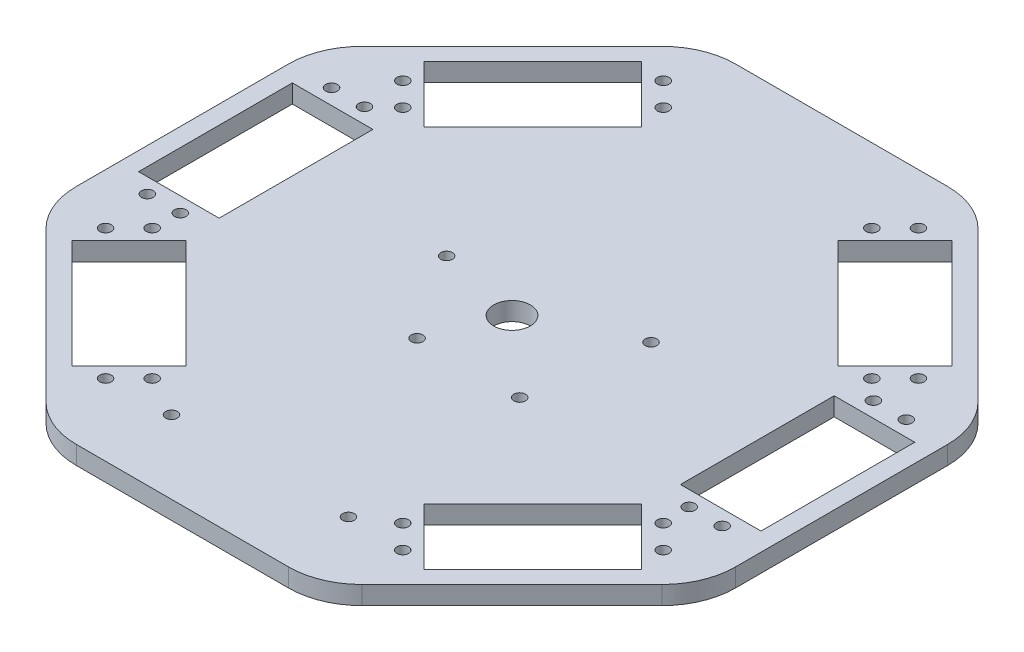
SolidWorks part; units mm, degrees
ref_plane "Front Plane" through (0, 0, 0) normal (0, 0, 1) x (1, 0, 0)
ref_plane "Top Plane" through (0, 0, 0) normal (0, 1, 0) x (1, 0, 0)
ref_plane "Right Plane" through (0, 0, 0) normal (1, 0, 0) x (0, 0, -1)
sketch "Sketch1" plane through (0, 0, 0) normal (0, 1, 0) x (1, 0, 0)
  line L1 (-90, -37.2792) -> (-37.2792, -90)
  line L2 (-37.2792, -90) -> (37.2792, -90)
  line L3 (37.2792, -90) -> (90, -37.2792)
  line L4 (90, -37.2792) -> (90, 37.2792)
  line L5 (90, 37.2792) -> (37.2792, 90)
  line L6 (37.2792, 90) -> (-37.2792, 90)
  line L7 (-37.2792, 90) -> (-90, 37.2792)
  line L8 (-90, 37.2792) -> (-90, -37.2792)
  line L12 (63.6396, -63.6396) -> (0, 0) construction
  line L21 (-20.4, -34.5422) -> (-34.5422, -20.4)
  line L22 (-20.4, -34.5422) -> (-50.0985, -64.2407)
  line L23 (-50.0985, -64.2407) -> (-64.2407, -50.0985)
  line L24 (-34.5422, -20.4) -> (-64.2407, -50.0985)
  line L25 (-38.85, -10) -> (-38.85, 10)
  line L26 (-38.85, -10) -> (-80.85, -10)
  line L27 (-80.85, -10) -> (-80.85, 10)
  line L28 (-38.85, 10) -> (-80.85, 10)
  line L29 (-34.5422, 20.4) -> (-20.4, 34.5422)
  line L30 (-34.5422, 20.4) -> (-64.2407, 50.0985)
  line L31 (-64.2407, 50.0985) -> (-50.0985, 64.2407)
  line L32 (-20.4, 34.5422) -> (-50.0985, 64.2407)
  line L37 (20.4, 34.5422) -> (34.5422, 20.4)
  line L38 (20.4, 34.5422) -> (50.0985, 64.2407)
  line L39 (50.0985, 64.2407) -> (64.2407, 50.0985)
  line L40 (34.5422, 20.4) -> (64.2407, 50.0985)
  line L41 (38.85, 10) -> (38.85, -10)
  line L42 (38.85, 10) -> (80.85, 10)
  line L43 (80.85, 10) -> (80.85, -10)
  line L44 (38.85, -10) -> (80.85, -10)
  circle A0 centre (0, 0) radius 90 construction
  circle A13 centre (0, 0) radius 90 construction
  circle A14 centre (-27.7186, -21.3546) radius 2.5
  circle A15 centre (-21.3546, -27.7186) radius 2.5
  circle A16 centre (-56.9221, -63.2861) radius 2.5
  circle A17 centre (-63.2861, -56.9221) radius 2.5
  circle A18 centre (0, 0) radius 90 construction
  circle A19 centre (-34.7, 4.5) radius 2.5
  circle A20 centre (-34.7, -4.5) radius 2.5
  circle A21 centre (-85, -4.5) radius 2.5
  circle A22 centre (-85, 4.5) radius 2.5
  circle A23 centre (0, 0) radius 90 construction
  circle A24 centre (-21.3546, 27.7186) radius 2.5
  circle A25 centre (-27.7186, 21.3546) radius 2.5
  circle A26 centre (-63.2861, 56.9221) radius 2.5
  circle A27 centre (-56.9221, 63.2861) radius 2.5
  circle A28 centre (0, 0) radius 90 construction
  circle A33 centre (0, 0) radius 90 construction
  circle A34 centre (27.7186, 21.3546) radius 2.5
  circle A35 centre (21.3546, 27.7186) radius 2.5
  circle A36 centre (56.9221, 63.2861) radius 2.5
  circle A37 centre (63.2861, 56.9221) radius 2.5
  circle A38 centre (0, 0) radius 90 construction
  circle A39 centre (34.7, -4.5) radius 2.5
  circle A40 centre (34.7, 4.5) radius 2.5
  circle A41 centre (85, 4.5) radius 2.5
  circle A42 centre (85, -4.5) radius 2.5
  circle A43 centre (0, 0) radius 90 construction
  point P15 (63.6396, -63.6396)
  point P16 (60.1041, -60.1041)
  point P17 (57.1696, -57.1696)
  point P121 (0, 0)
  dimension "D1" = 90
  dimension "D12" = 8
extrude "Baseplate" add sketch "Sketch1" along normal blind 5 contours L7 L8 L1 L2 L3 L4 L5 L6 A42 A41 A40 A39 A37 A36 A35 A34 A27 A26 A25 A24 A22 A21 A20 A19 A17 A16 A15 A14 L44 L41 | L29 L32 L31 L30 | L37 L40 L39 L38 | L41 L44 L43 L42 | L25 L28 L27 L26 | A27 | A26 | A25 | A24 | A22 | A21 | A19 | A20 | A14 | A15 | A17 | A16 | A40 | A41 | A42 | A35 | A34 | A39 | A37 | A36 | L21 L24 L23 L22 region at (1.7472, 0, 1.7472) region at (-59.85, 0, 0) region at (-42.3203, 0, -42.3203) region at (42.3203, 0, -42.3203) region at (59.85, 0, 0) region at (-27.7186, 0, 21.3546) region at (-21.3546, 0, 27.7186) region at (-56.9221, 0, 63.2861) region at (-63.2861, 0, 56.9221) region at (-34.7, 0, -4.5) region at (-34.7, 0, 4.5) region at (-85, 0, 4.5) region at (-85, 0, -4.5) region at (-21.3546, 0, -27.7186) region at (-27.7186, 0, -21.3546) region at (-63.2861, 0, -56.9221) region at (-56.9221, 0, -63.2861) region at (34.7, 0, -4.5) region at (85, 0, -4.5) region at (85, 0, 4.5)
fillet "Fillet1" radius 20 8 edges at (-90, 2.5, -37.2792) (-37.2792, 2.5, -90) (37.2792, 2.5, -90) (90, 2.5, -37.2792) (90, 2.5, 37.2792) (37.2792, 2.5, 90) (-37.2792, 2.5, 90) (-90, 2.5, 37.2792)
sketch "Sketch2" plane through (0, 5, 0) normal (0, 1, 0) x (1, 0, 0)
  line L0 (90, -28.9949) -> (90, 28.9949) construction
  line L1 (63, 25.0051) -> (85, 25.0051)
  line L2 (63, 25.0051) -> (63, -16.9949)
  line L3 (63, -16.9949) -> (85, -16.9949)
  line L4 (85, 25.0051) -> (85, -16.9949)
  circle A0 centre (78.5, 29.2051) radius 1.6
  circle A1 centre (69.5, 29.2051) radius 1.6
  circle A2 centre (69.5, -21.0949) radius 1.6
  circle A3 centre (78.5, -21.0949) radius 1.6
  point P8 (74, 25.0051)
  dimension "D1" = 3.2
  dimension "D2" = 9
  dimension "D3" = 50.3
  dimension "D4" = 22
  dimension "D5" = 42
  dimension "D6" = 4.2
  dimension "D7" = 4.5
  dimension "D8" = 5
  dimension "D9" = 12
extrude "Servo hole" cut sketch "Sketch2" against normal through all contours A0 | L4 L1 L2 L3 | A2 | A3 | A1 region at (74, 5, -4.0051) region at (78.5, 5, -29.2051) region at (69.5, 5, 21.0949) region at (78.5, 5, 21.0949)
sketch "Sketch3" plane through (0, 5, 0) normal (0, 1, 0) x (1, 0, 0)
  circle A0 centre (0, 0) radius 5
  dimension "D1" = 10
extrude "Center hole" cut sketch "Sketch3" against normal through all
pattern_circular "Servo hole pattern" count 8 over 360 about axis through (0, 5, 0) along (0, 1, 0) skipping 2, 3, 4, 5, 6 of "Servo hole"
sketch "Sketch4" plane through (0, 5, 0) normal (0, 1, 0) x (1, 0, 0)
  line L0 (-28.9949, -90) -> (28.9949, -90) construction
  line L1 (-90, 28.9949) -> (-90, -28.9949) construction
  circle A0 centre (-23, 5.1332) radius 1.6
  circle A1 centre (-23, -70) radius 1.6
  circle A2 centre (25.3362, 12.6262) radius 1.6
  circle A3 centre (25.3362, -70) radius 1.6
  circle A4 centre (-7.5585, -18.3745) radius 1.6
  circle A5 centre (20.4577, -18.3745) radius 1.6
  dimension "D1" = 3.2
  dimension "D8" = 20
  dimension "D2" = 7.493
  dimension "D3" = 48.3362
  dimension "D4" = 31.0007
  dimension "D5" = 51.6255
  dimension "D6" = 4.8785
  dimension "D7" = 28.0162
  dimension "D9" = 67
extrude "Arduino Screw holes" cut sketch "Sketch4" against normal through all
ref_plane "Midplane" through (0, 0, 0) normal (1, 0, 0) x (0, 0, -1)
mirror "Mirror1" about plane through (0, 0, 0) normal (1, 0, 0) of "Servo hole pattern", "Servo hole"
